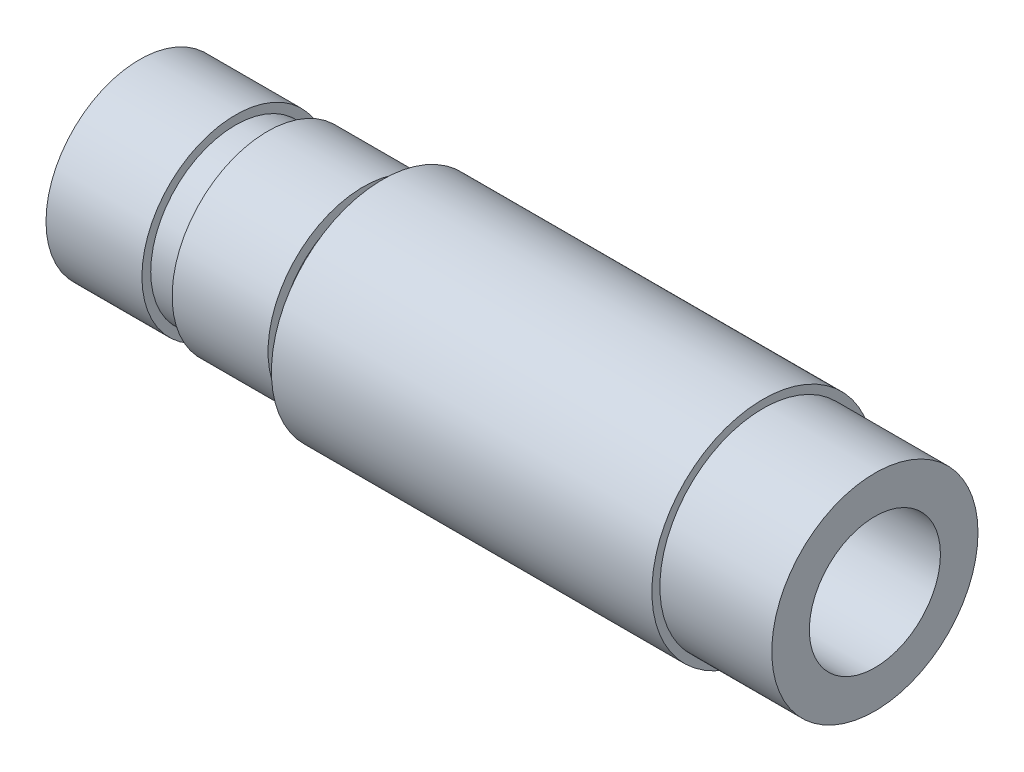
SolidWorks part; units mm, degrees
ref_plane "Front Plane" through (0, 0, 0) normal (0, 0, 1) x (1, 0, 0)
ref_plane "Top Plane" through (0, 0, 0) normal (0, 1, 0) x (1, 0, 0)
ref_plane "Right Plane" through (0, 0, 0) normal (1, 0, 0) x (0, 0, -1)
sketch "Sketch2" plane through (0, 0, 0) normal (0, 0, 1) x (1, 0, 0)
  line L0 (277.539, 63.4078) -> (314.539, 63.3714) construction
  line L1 (307.7622, 76.8439) -> (284.7622, 76.8439)
  line L2 (304.2622, 80.3189) -> (304.2622, 80.0689)
  line L3 (304.2622, 80.0689) -> (307.7622, 80.0689)
  line L6 (307.7622, 76.8439) -> (307.7622, 80.0689)
  line L8 (291.7622, 79.8239) -> (291.7622, 79.4939)
  line L11 (284.7622, 76.8439) -> (284.7622, 79.7689)
  line L12 (284.7622, 79.7689) -> (287.7622, 79.7689)
  line L13 (287.7622, 79.7689) -> (287.7622, 79.4939)
  line L14 (287.7622, 79.4939) -> (288.7622, 79.4939)
  line L15 (288.7622, 79.4939) -> (288.7622, 79.8239)
  line L16 (288.7622, 79.8239) -> (291.7622, 79.8239)
  line L17 (291.7622, 79.4939) -> (292.3622, 79.4939)
  line L18 (292.3622, 79.4939) -> (292.3622, 80.3189)
  line L19 (292.3622, 80.3189) -> (304.2622, 80.3189)
  dimension "D6" = 2.65
  dimension "D1" = 37
  dimension "D2" = 23
  dimension "D3" = 3.5
  dimension "D4" = 3
  dimension "D5" = 1
  dimension "D7" = 2.925
  dimension "D8" = 2.98
  dimension "D9" = 2.65
  dimension "D10" = 3
  dimension "D11" = 3.475
  dimension "D12" = 3.225
revolve "Revolve4" add sketch "Sketch2" angle 360 about L1 region at (296.6049, 78.477, 0)
hole_wizard "Tap Drill for M5 Tap1" positions "Sketch4" profile "Sketch3" hole size "M5" standard "ISO"
sketch "Sketch4" plane through (307.7622, 0, 0) normal (1, 0, 0) x (0, 0, -1)
  point P0 (0, 76.8439)
sketch "Sketch3" plane through (307.7622, 76.8439, 0) normal (0, 1, 0) x (0, 0, -1)
  line L0 (0, 0) -> (0, 6.7318)
  line L1 (0, 6.7318) -> (2.05, 5.5)
  line L2 (2.05, 5.5) -> (2.05, 0)
  line L5 (2.05, 0) -> (0, 0)
  line L10 (0, 6.7318) -> (-2.05, 5.5) construction
  line L11 (0, -6.35) -> (0, 107.95) construction
  dimension "Hole Dia." = 4.1
  dimension "Hole Depth" = 5.5
  dimension "Drill Angle" = 118
sketch "Sketch5" plane through (284.7622, 0, 0) normal (-1, 0, 0) x (0, 0, 1)
  circle A0 centre (0, 76.8439) radius 1.75
extrude "Cut-Extrude1" cut sketch "Sketch5" against normal blind 29.8
